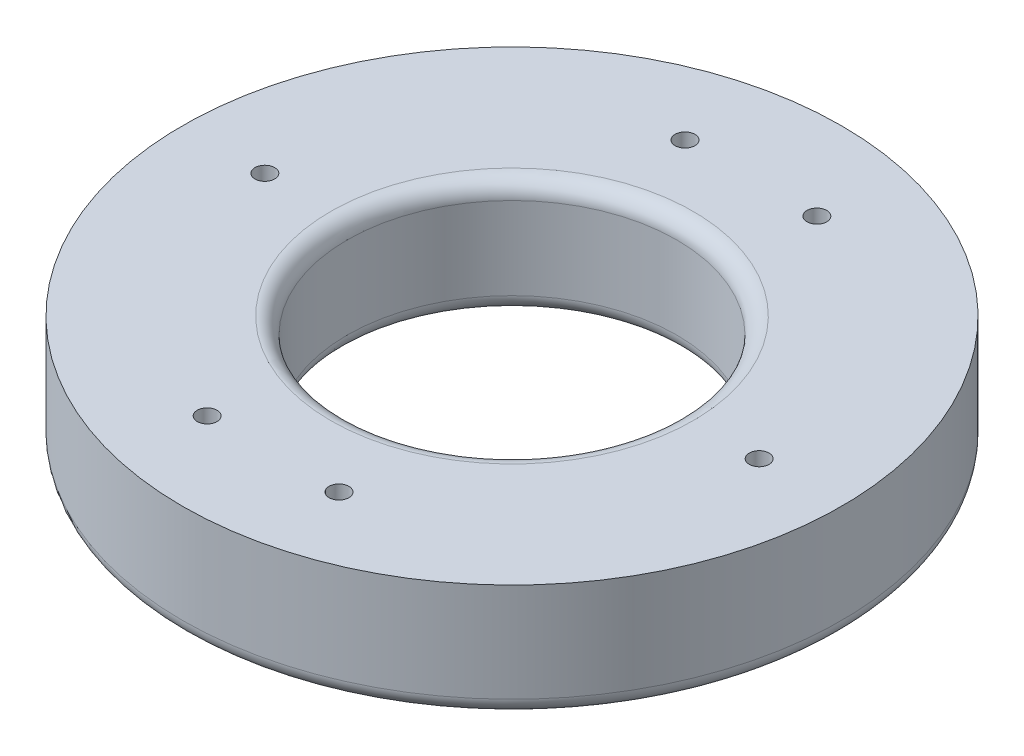
SolidWorks part; units mm, degrees
ref_plane "Спереди" through (0, 0, 0) normal (0, 0, 1) x (1, 0, 0)
ref_plane "Сверху" through (0, 0, 0) normal (0, 1, 0) x (1, 0, 0)
ref_plane "Справа" through (0, 0, 0) normal (1, 0, 0) x (0, 0, -1)
sketch "Sketch1" plane through (0, 0, 0) normal (0, 1, 0) x (1, 0, 0)
  line L0 (-11.7247, 0) -> (16.8046, 0) construction
  line L1 (0, 7.3106) -> (0, -15.7423) construction
  circle A0 centre (0, 0) radius 20
  circle A1 centre (-4, 14.5) radius 0.6
  circle A2 centre (-4, -14.5) radius 0.6
  circle A3 centre (15, 0) radius 0.6
  circle A4 centre (-15, 0) radius 0.6
  circle A5 centre (4, 14.5) radius 0.6
  circle A6 centre (4, -14.5) radius 0.6
  circle A8 centre (0, 0) radius 10
  dimension "D1" = 40
  dimension "D7" = 1.2
  dimension "D8" = 1.2
  dimension "D9" = 1.2
  dimension "D10" = 1.2
  dimension "D11" = 1.2
  dimension "D12" = 1.2
  dimension "D18" = 20
  dimension "D2" = 15
  dimension "D3" = 4
  dimension "D4" = 14.5
  dimension "D5" = 14.5
  dimension "D6" = 4
  dimension "D13" = 15
  dimension "D14" = 4
  dimension "D15" = 14.5
  dimension "D16" = 14.5
  dimension "D17" = 4
extrude "Boss-Extrude1" add sketch "Sketch1" along normal blind 7
fillet "Fillet1" radius 1 3 edges at (0, 0, 20) (0, 0, 10) (0, 7, 10)
